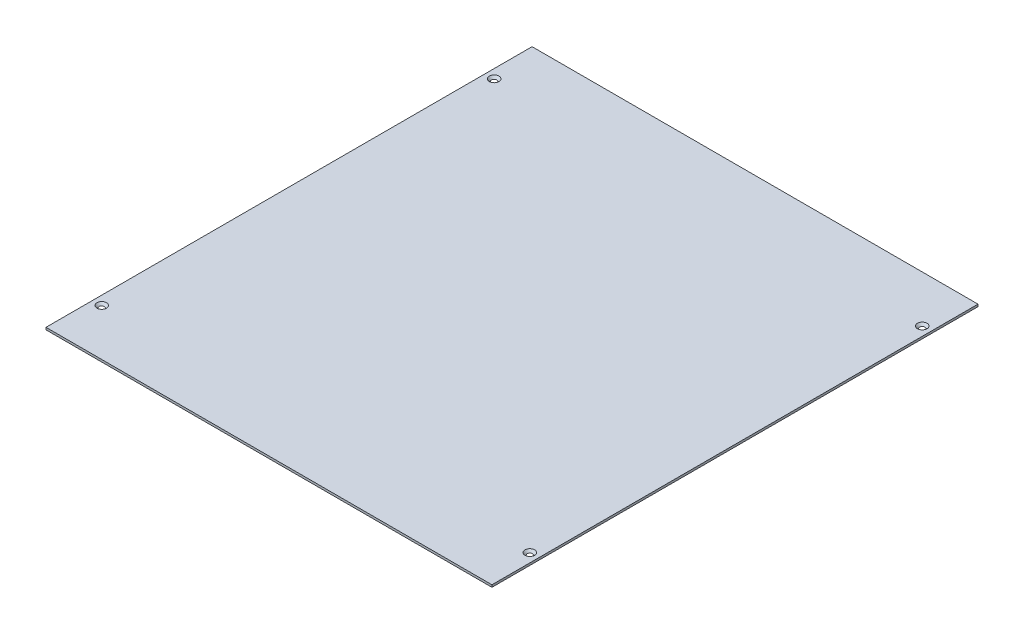
SolidWorks part; units mm, degrees
material "1060 Сплав"
ref_plane "Front" through (0, 0, 0) normal (0, 0, 1) x (1, 0, 0)
ref_plane "Top" through (0, 0, 0) normal (0, 1, 0) x (1, 0, 0)
ref_plane "Right" through (0, 0, 0) normal (1, 0, 0) x (0, 0, -1)
sketch "Эскиз1" plane through (0, 0, 0) normal (0, 1, 0) x (1, 0, 0)
  line L1 (0, 0) -> (400, 0)
  line L2 (0, 0) -> (0, 436)
  line L3 (0, 436) -> (400, 436)
  line L4 (400, 0) -> (400, 436)
  circle A0 centre (8, 394) radius 2.25
  circle A1 centre (392, 394) radius 2.25
  circle A2 centre (392, 42) radius 2.25
  circle A3 centre (8, 42) radius 2.25
  dimension "D3" = 4.5
  dimension "D4" = 42
  dimension "D5" = 8
  dimension "D8" = 8
  dimension "D9" = 42
  dimension "D1" = 436
  dimension "D2" = 400
  dimension "D6" = 2
  dimension "D7" = 2
extrude "Бобышка-Вытянуть1" add sketch "Эскиз1" along normal blind 2
chamfer "Фаска1" distance 2.05 angle 45 4 edges at (392, 2, -391.75) (392, 2, -39.75) (8, 2, -391.75) (8, 2, -39.75)
